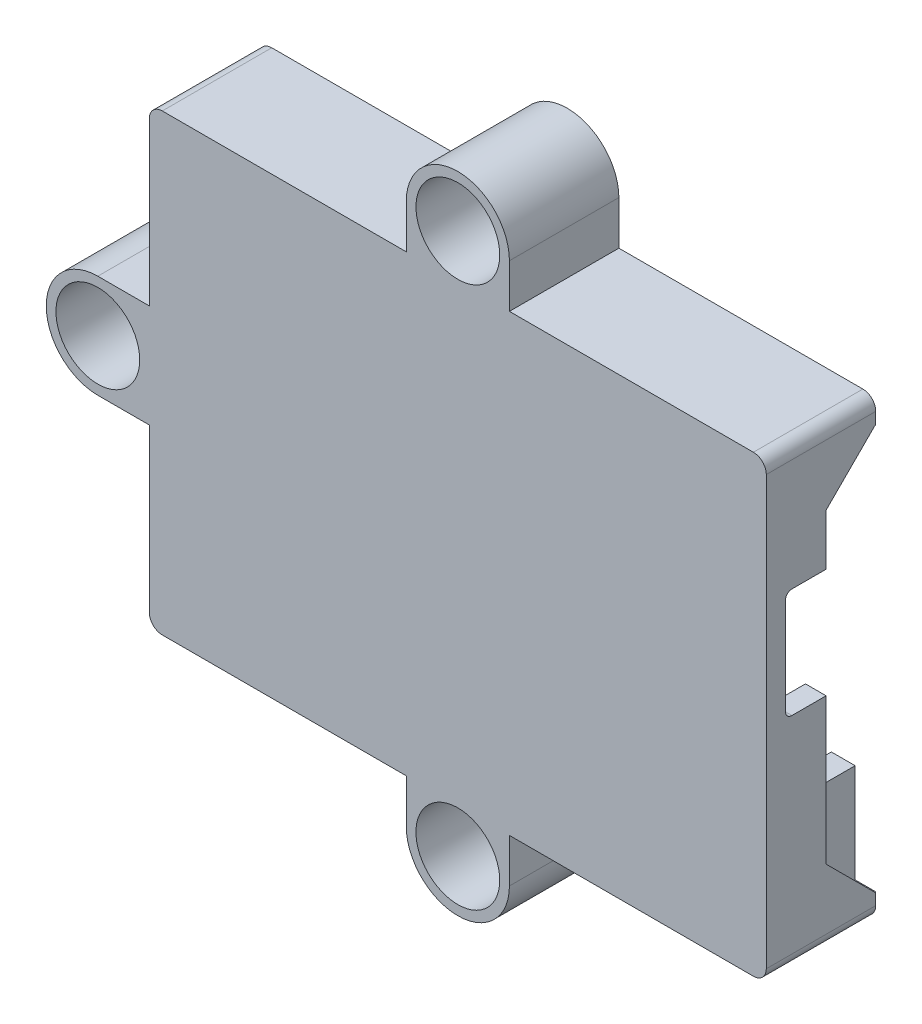
SolidWorks part; units mm, degrees
ref_plane "Front Plane" through (0, 0, 0) normal (0, 0, 1) x (1, 0, 0)
ref_plane "Top Plane" through (0, 0, 0) normal (0, 1, 0) x (1, 0, 0)
ref_plane "Right Plane" through (0, 0, 0) normal (1, 0, 0) x (0, 0, -1)
sketch "Sketch1" plane through (0, 0, 0) normal (0, 0, 1) x (1, 0, 0)
  line L0 (-22.325, 16) -> (22.325, 16)
  line L1 (-23.925, -17.6) -> (23.925, -17.6)
  line L2 (-23.925, -17.6) -> (-23.925, 17.6)
  line L3 (-23.925, 17.6) -> (23.925, 17.6)
  line L4 (23.925, -17.6) -> (23.925, 17.6)
  line L5 (22.325, -16) -> (22.325, 16)
  line L6 (-22.325, -16) -> (22.325, -16)
  line L7 (-22.325, -16) -> (-22.325, 16)
  line L8 (22.925, 17.6) -> (4, 17.6) construction
  line L9 (-23.925, 16.6) -> (-23.925, 4) construction
  line L10 (23.925, 15.6) -> (23.925, 16.6) construction
  line L11 (-22.925, -17.6) -> (-4, -17.6) construction
  dimension "D1" = 1.6
extrude "Boss-Extrude1" add sketch "Sketch1" along normal offset from surface (6.99 mm away) 0.5 offset beyond the face yes
sketch "Sketch2" plane through (0, 0, 6.99) normal (0, 0, 1) x (1, 0, 0)
  line L4 (23.925, 17.6) -> (-23.925, 17.6)
  line L5 (-23.925, 17.6) -> (-23.925, -17.6)
  line L6 (-23.925, -17.6) -> (23.925, -17.6)
  line L7 (23.925, -17.6) -> (23.925, 17.6)
  line L8 (23.925, 17.6) -> (-23.925, 17.6)
  line L9 (-23.925, 17.6) -> (-23.925, -17.6)
  line L10 (-23.925, -17.6) -> (23.925, -17.6)
  line L11 (23.925, -17.6) -> (23.925, 17.6)
  dimension "D1" = 0
extrude "Boss-Extrude2" add sketch "Sketch2" along normal blind 1.5
sketch "Sketch3" plane through (23.925, 0, 0) normal (1, 0, 0) x (0, 0, -1)
  line L3 (-0.0707, 15.6707) -> (0, 15.6707)
  line L4 (0, -17.6) -> (0, 17.6) construction
  line L5 (-0.0707, -15.6707) -> (0, -15.6707)
  line L6 (-0.0707, 15.6707) -> (-3.85, 11.8914)
  line L7 (-3.85, 11.8914) -> (-3.85, -11.8914)
  line L8 (-3.85, -11.8914) -> (-0.0707, -15.6707)
  line L9 (-0.0707, 15.6707) -> (-3.85, 11.8914)
  line L10 (-3.85, 11.8914) -> (-3.85, -11.8914)
  line L11 (-3.85, -11.8914) -> (-0.0707, -15.6707)
  line L12 (0, 15.6707) -> (0, -15.6707)
  dimension "D1" = 0.1
extrude "Cut-Extrude1" cut sketch "Sketch3" against normal up to next
sketch "Sketch4" plane through (23.925, 0, 0) normal (1, 0, 0) x (0, 0, -1)
  line L0 (-3.5, 7.9205) -> (-3.5, -0.5795) construction
  line L1 (-3.5, -0.5795) -> (-7, -0.5795) construction
  line L2 (-7, 7.9205) -> (-7, -0.5795) construction
  line L3 (-3.5, 7.9205) -> (-7, 7.9205) construction
  line L4 (-3.5, 7.9205) -> (-3.5, -0.5795)
  line L5 (-3.5, -0.5795) -> (-7, -0.5795)
  line L6 (-7, 7.9205) -> (-7, -0.5795)
  line L7 (-3.5, 7.9205) -> (-7, 7.9205)
extrude "Cut-Extrude2" cut sketch "Sketch4" against normal up to surface (1.6 mm away) up to face at (22.325, 0, 2.1821)
sketch "Sketch6" plane through (0, -17.6, 0) normal (0, -1, 0) x (1, 0, 0)
  line L0 (20.48, -0.28) -> (20.48, 6.32) construction
  line L1 (20.48, -0.28) -> (10.08, -0.28) construction
  line L2 (10.08, -0.28) -> (10.08, 6.32) construction
  line L3 (20.48, 6.32) -> (10.08, 6.32) construction
  line L4 (20.48, -0.28) -> (20.48, 6.32)
  line L5 (20.48, -0.28) -> (10.08, -0.28)
  line L6 (10.08, -0.28) -> (10.08, 6.32)
  line L7 (20.48, 6.32) -> (10.08, 6.32)
extrude "Cut-Extrude3" cut sketch "Sketch6" against normal up to next
fillet "Fillet1" radius 1 4 edges at (-23.925, 17.6, 4.245) (23.925, 17.6, 4.245) (-23.925, -17.6, 4.245) (23.925, -17.6, 4.245)
fillet "Fillet2" radius 0.5 4 edges at (23.125, -0.5795, 7) (20.48, -16.8, 6.32) (23.125, 7.9205, 7) (10.08, -16.8, 6.32)
sketch "Sketch7" plane through (0, 0, 8.49) normal (0, 0, 1) x (1, 0, 0)
  line L0 (4, -17.6) -> (4, -21) construction
  line L1 (-4, -17.6) -> (-4, -21) construction
  line L2 (4, -17.6) -> (4, -21)
  line L3 (-4, -17.6) -> (-4, -21)
  line L4 (-4, -17.6) -> (4, -17.6)
  line L5 (-4, 17.6) -> (-4, 21) construction
  line L6 (4, 17.6) -> (4, 21) construction
  line L7 (-4, 17.6) -> (-4, 21)
  line L8 (4, 17.6) -> (4, 21)
  line L9 (4, 17.6) -> (-4, 17.6)
  line L10 (-23.925, -4) -> (-27.925, -4) construction
  line L11 (-23.925, 4) -> (-27.925, 4) construction
  line L12 (-23.925, -4) -> (-27.925, -4)
  line L13 (-23.925, 4) -> (-27.925, 4)
  line L14 (-23.925, 4) -> (-23.925, -4)
  arc A1 (-4, -21) -> (4, -21) centre (0, -21) ccw construction
  arc A3 (-4, -21) -> (4, -21) centre (0, -21) ccw
  arc A5 (4, 21) -> (-4, 21) centre (0, 21) ccw construction
  arc A7 (4, 21) -> (-4, 21) centre (0, 21) ccw
  circle A8 centre (0, 21) radius 2
  circle A9 centre (0, -21) radius 2
  circle A10 centre (-27.925, 0) radius 2
  arc A11 (-27.925, 4) -> (-27.925, -4) centre (-27.925, 0) ccw construction
  arc A12 (-27.925, 4) -> (-27.925, -4) centre (-27.925, 0) ccw
  dimension "D1" = 4
extrude "Boss-Extrude3" add sketch "Sketch7" against normal up to surface (8.49 mm away) up to face at (-0.2286, 3.7037, 0)
sketch "Sketch8" plane through (0, 0, 8.49) normal (0, 0, 1) x (1, 0, 0)
  circle A0 centre (0, 21) radius 3.25
  circle A1 centre (0, -21) radius 3.25
  circle A2 centre (-27.925, 0) radius 3.25
  dimension "D1" = 6.5
extrude "Cut-Extrude4" cut sketch "Sketch8" against normal offset from surface (6.49 mm away) 2 up to face at (22.3703, -16.4784, 0)
sketch "Sketch9" plane through (0, 0, 0) normal (0, 0, -1) x (-1, 0, 0)
  line L0 (-4, -17.6) -> (-4, -16) construction
  line L1 (-10.08, -16) -> (-8.48, -16)
  line L2 (-10.08, -16) -> (-10.08, -8)
  line L3 (-10.08, -8) -> (-8.48, -8)
  line L4 (-8.48, -16) -> (-8.48, -8)
  line L5 (22.325, -16) -> (-10.08, -16) construction
  line L6 (-22.325, -0.5795) -> (-22.325, -11.8914) construction
  line L7 (-20.48, -16) -> (-22.325, -16)
  line L8 (-20.48, -16) -> (-20.48, -8)
  line L9 (-20.48, -8) -> (-22.325, -8)
  line L10 (-22.325, -16) -> (-22.325, -8)
  dimension "D1" = 8
extrude "Boss-Extrude4" add sketch "Sketch9" against normal up to surface (6.99 mm away) up to face at (7.4417, 1.2235, 6.99)
